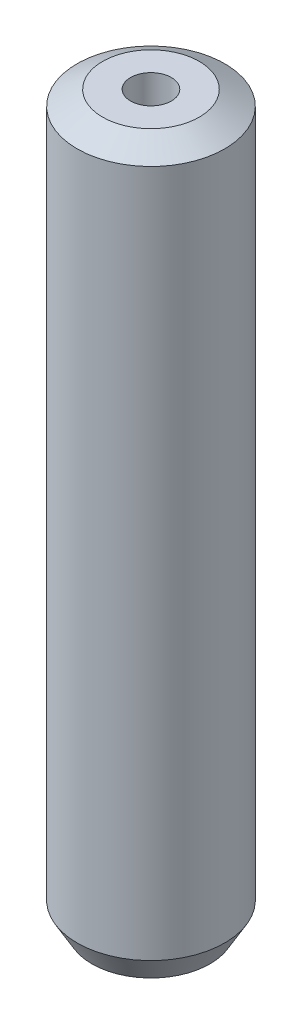
SolidWorks part; units mm, degrees
ref_plane "Front Plane" through (0, 0, 0) normal (0, 0, 1) x (1, 0, 0)
ref_plane "Top Plane" through (0, 0, 0) normal (0, 1, 0) x (1, 0, 0)
ref_plane "Right Plane" through (0, 0, 0) normal (1, 0, 0) x (0, 0, -1)
sketch "Sketch1" plane through (0, 0, 0) normal (0, 1, 0) x (1, 0, 0)
  circle A0 centre (0, 0) radius 7.5
  dimension "SHAFT_OD" = 15
extrude "Boss-Extrude1" add sketch "Sketch1" along normal blind 73.9692
sketch "Sketch2" plane through (0, 0, 0) normal (0, 1, 0) x (1, 0, 0)
  circle A0 centre (0, 0) radius 2.0731
  dimension "BORE_D" = 4.1461
extrude "Cut-Extrude1" cut sketch "Sketch2" along normal through all
chamfer "Chamfer1" distance 1.4953 angle 60 2 edges at (0, 73.9692, 7.5) (0, 0, 7.5) first distance on face at (0, 73.9692, 7.5) first distance on face at (0, 0, 2.0731)
